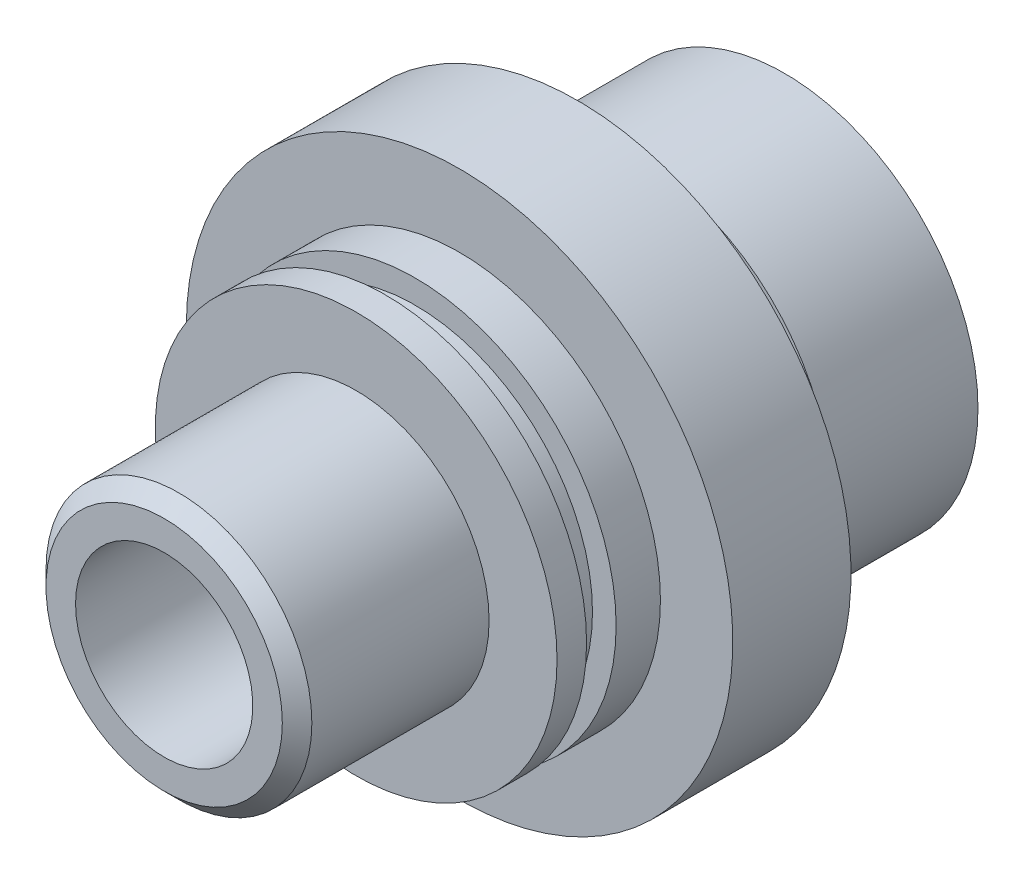
SolidWorks part; units mm, degrees
ref_plane "Front Plane" through (0, 0, 0) normal (0, 0, 1) x (1, 0, 0)
ref_plane "Top Plane" through (0, 0, 0) normal (0, 1, 0) x (1, 0, 0)
ref_plane "Right Plane" through (0, 0, 0) normal (1, 0, 0) x (0, 0, -1)
sketch "Sketch1" plane through (0, 0, 0) normal (0, 0, 1) x (1, 0, 0)
  circle A0 centre (0, 0) radius 3
  circle A1 centre (0, 0) radius 9.25
extrude "Boss-Extrude1" add sketch "Sketch1" along normal blind 21
sketch "Sketch2" plane through (0, 0, 21) normal (0, 0, 1) x (1, 0, 0)
  circle A0 centre (0, 0) radius 4.5
extrude "Cut-Extrude1" cut sketch "Sketch2" against normal blind 6.5 flip side to cut
sketch "Sketch3" plane through (0, 0, 14.5) normal (0, 0, 1) x (1, 0, 0)
  circle A0 centre (0, 0) radius 6.8
extrude "Cut-Extrude2" cut sketch "Sketch3" against normal blind 3.5 flip side to cut
sketch "Sketch4" plane through (0, 0, 14.5) normal (0, 0, 1) x (1, 0, 0)
  circle A0 centre (0, 0) radius 6
extrude "Cut-Extrude3" cut sketch "Sketch4" against normal blind 1 from offset 1 flip side to cut offset against normal yes
sketch "Sketch5" plane through (0, 0, 0) normal (0, 0, -1) x (-1, 0, 0)
  circle A0 centre (0, 0) radius 6.55
extrude "Cut-Extrude5" cut sketch "Sketch5" against normal blind 7 flip side to cut
sketch "Sketch6" plane through (0, 0, 0) normal (0, 0, -1) x (-1, 0, 0)
  circle A0 centre (0, 0) radius 6
  circle A1 centre (0, 0) radius 7.5
extrude "Cut-Extrude6" cut sketch "Sketch6" against normal blind 3 from offset 5 offset against normal yes
chamfer "Chamfer1" distance 0.5 angle 45 1 edges at (4.5, 0, 21)
